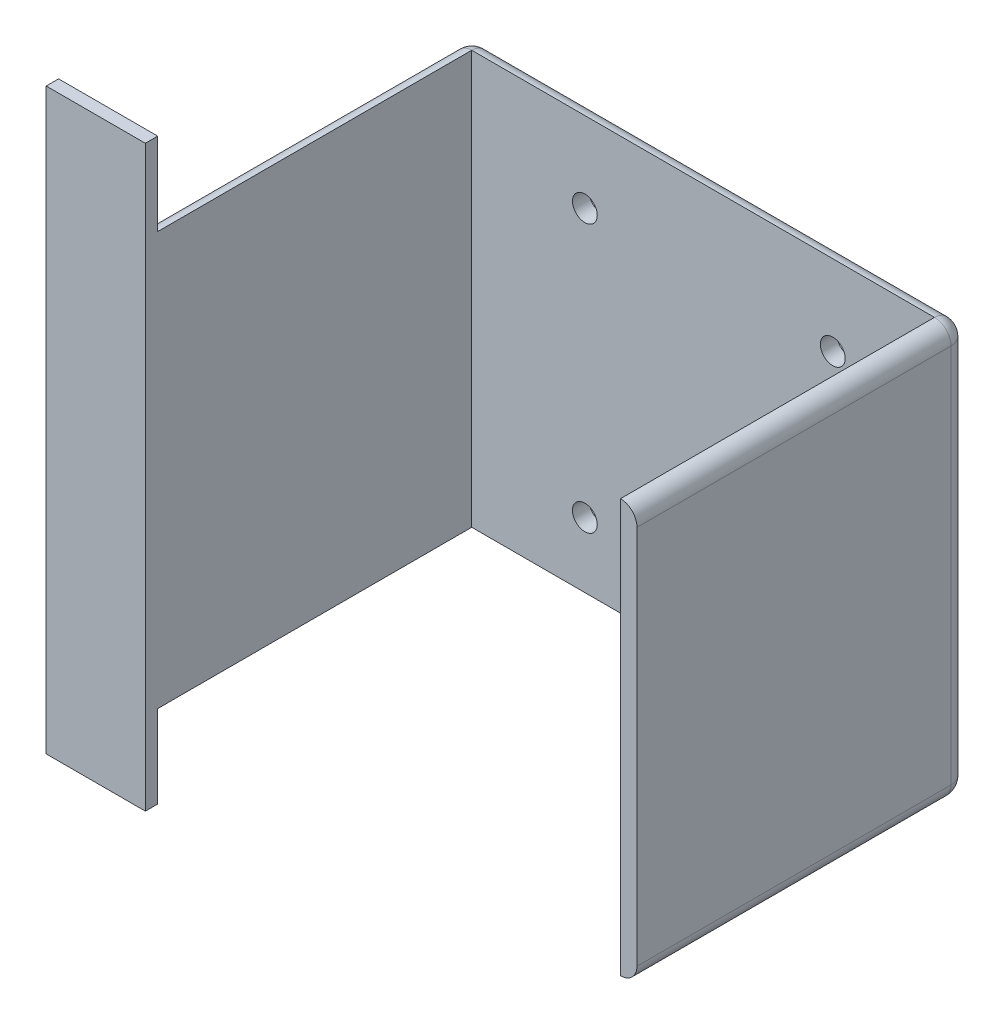
SolidWorks part; units mm, degrees
ref_plane "Front Plane" through (0, 0, 0) normal (0, 0, 1) x (1, 0, 0)
ref_plane "Top Plane" through (0, 0, 0) normal (0, 1, 0) x (1, 0, 0)
ref_plane "Right Plane" through (0, 0, 0) normal (1, 0, 0) x (0, 0, -1)
sketch "Sketch1" plane through (0, 0, 0) normal (0, 0, 1) x (1, 0, 0)
  line L1 (-30, 25) -> (30, 25)
  line L2 (-30, 25) -> (-30, -25)
  line L3 (-30, -25) -> (30, -25)
  line L4 (30, 25) -> (30, -25)
  line L5 (-30, 25) -> (30, -25) construction
  line L6 (-30, -25) -> (30, 25) construction
  point P0 (0, 0)
  dimension "D1" = 60
  dimension "D2" = 50
extrude "Boss-Extrude1" add sketch "Sketch1" along normal blind 40
sketch "Sketch2" plane through (0, 0, 40) normal (0, 0, 1) x (1, 0, 0)
  line L0 (30, -25) -> (30, 25) construction
  line L1 (-40, 35) -> (30, 35)
  line L2 (-40, 35) -> (-40, -35)
  line L3 (-40, -35) -> (30, -35)
  line L4 (30, 35) -> (30, -35)
  line L5 (30, 25) -> (-30, 25) construction
  line L6 (-30, 25) -> (-30, -25) construction
  line L8 (-30, -25) -> (30, -25) construction
  dimension "D1" = 10
  dimension "D2" = 10
  dimension "D3" = 10
extrude "Boss-Extrude2" add sketch "Sketch2" along normal blind 1.5 contours L2 L1 L4 L3
shell "Shell1" thickness 2 removed face at (-5, 0, 41.5)
hole_wizard "Ø3.0mm Dowel Hole2" positions "Sketch5" profile "Sketch6" hole size "Ø3.0" standard "ANSI Metric"
sketch "Sketch5" plane through (-311.7811, -231.688, 0) normal (0, 0, -1) x (-1, 0, 0)
  point P0 (-327.4711, 246.9697)
  point P1 (-297.4711, 246.9697)
  point P2 (-297.4711, 214.5697)
  point P3 (-327.4711, 214.5697)
sketch "Sketch6" plane through (15.69, 15.2817, 0) normal (1, 0, 0) x (0, 1, 0)
  line L0 (0, 0) -> (0, 41.499)
  line L1 (0, 41.499) -> (1.5, 41.499)
  line L2 (1.5, 41.499) -> (1.5, 0)
  line L3 (1.5, 0) -> (0, 0)
  line L4 (0, -6.35) -> (0, 107.95) construction
  dimension "Thru Hole Dia." = 3
  dimension "Thru Hole Depth" = 41.499
fillet "Fillet1" radius 2 8 edges at (30, 0, 0) (0, 25, 0) (-30, 0, 0) (30, -25, 20) (-30, -25, 20) (-30, 25, 20) (30, 25, 20) (0, -25, 0)
sketch "Sketch8" plane through (0, -25, 0) normal (0, -1, 0) x (1, 0, 0)
  line L0 (-40, 41.5) -> (30, 41.5) construction
  line L1 (28, 2) -> (-28, 2)
  line L2 (28, 2) -> (28, 41.5)
  line L3 (28, 41.5) -> (-28, 41.5)
  line L4 (-28, 2) -> (-28, 41.5)
  line L5 (-28, 40) -> (-28, 2) construction
extrude "Cut-Extrude2" cut sketch "Sketch8" against normal through all both and the other way through all
sketch "Sketch9" plane through (30, 0, 0) normal (1, 0, 0) x (0, 0, -1)
  line L1 (-40, 35) -> (-41.5, 35)
  line L2 (-40, 35) -> (-40, -35)
  line L3 (-40, -35) -> (-41.5, -35)
  line L4 (-41.5, 35) -> (-41.5, -35)
extrude "Cut-Extrude3" cut sketch "Sketch9" against normal up to surface (2 mm away) up to face at (28, 0, 30.875)
equation "\"dist_to_lock\"= 1cm"
equation "\"door_depth\"= 4.7cm"
equation "\"D2@Sketch2\"=\"D1@Sketch2\""
equation "\"D3@Sketch2\"=\"D1@Sketch2\""
